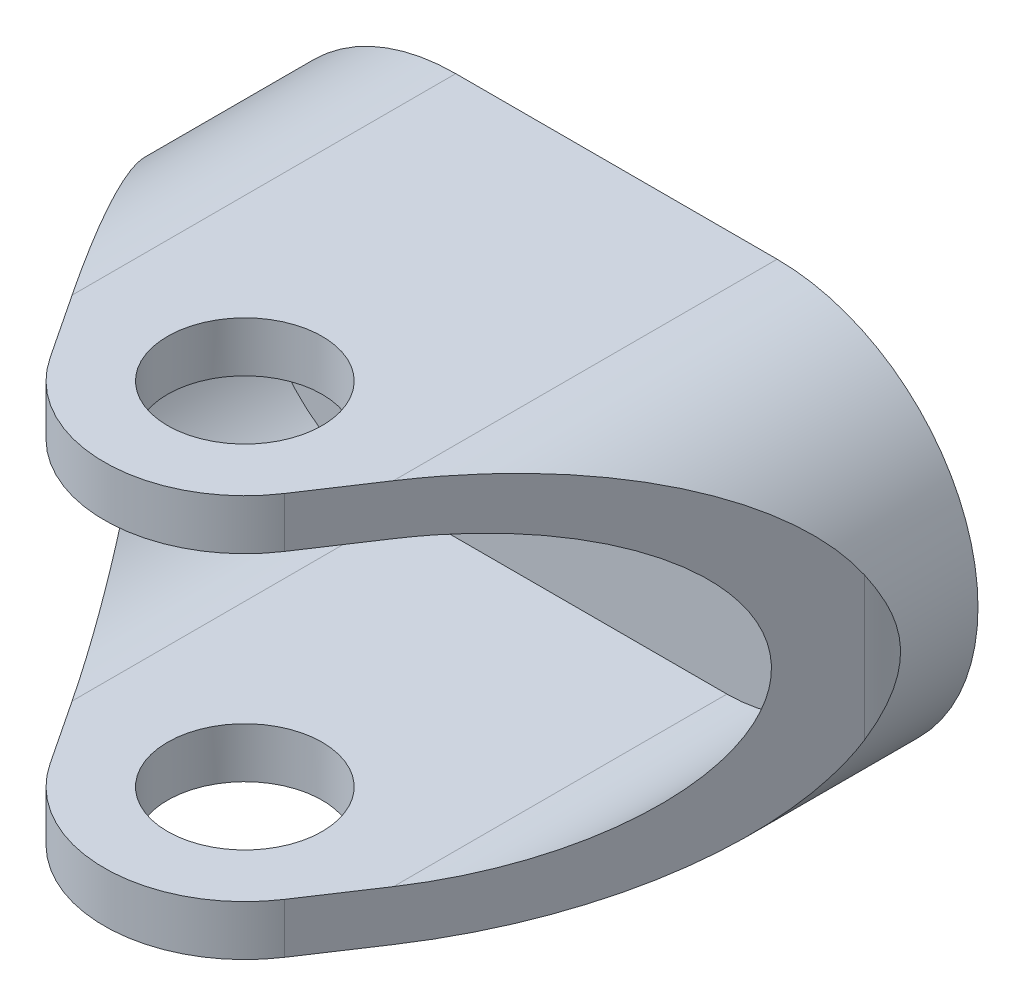
SolidWorks part; units mm, degrees
material "6061 Alloy"
ref_plane "Front Plane" through (0, 0, 0) normal (0, 0, 1) x (1, 0, 0)
ref_plane "Top Plane" through (0, 0, 0) normal (0, 1, 0) x (1, 0, 0)
ref_plane "Right Plane" through (0, 0, 0) normal (1, 0, 0) x (0, 0, -1)
sketch "Sketch1" plane through (0, 0, 0) normal (0, 1, 0) x (1, 0, 0)
  line L0 (-24.13, -19.05) -> (24.13, -19.05)
  line L1 (-24.13, -19.05) -> (-24.13, 19.05)
  line L2 (24.13, -19.05) -> (24.13, 19.05)
  line L3 (-24.13, 19.05) -> (24.13, 19.05)
  line L4 (-24.13, -19.05) -> (24.13, 19.05) construction
  line L5 (24.13, -19.05) -> (-24.13, 19.05) construction
  point P1 (0, 0)
  dimension "D1" = 38.1
  dimension "D2" = 48.26
extrude "Billet" add sketch "Sketch1" along normal blind 25.4
sketch "Sketch2" plane through (0, 25.4, 0) normal (0, 1, 0) x (1, 0, 0)
  line L1 (-7.4106, -9.3557) -> (-24.13, 15.875)
  line L3 (24.13, 19.05) -> (-24.13, 19.05) construction
  line L4 (-24.13, 15.875) -> (24.13, 15.875) construction
  line L5 (0, -14.605) -> (0, -11.9174) construction
  line L6 (-24.13, 15.875) -> (-24.13, -19.05)
  line L7 (-24.13, -19.05) -> (24.13, -19.05)
  line L8 (24.13, -19.05) -> (24.13, 15.875)
  line L9 (7.4106, -9.3557) -> (24.13, 15.875)
  arc A0 (7.4106, -9.3557) -> (-7.4106, -9.3557) centre (0, -4.445) cw
  circle A1 centre (0, -4.445) radius 4.8895
  line M1 (-24.13, 19.05) -> (-24.13, -19.05)
  line M2 (-24.13, -19.05) -> (24.13, -19.05)
  line M3 (24.13, -19.05) -> (24.13, 19.05)
  dimension "D1" = 8.89
  dimension "D3" = 9.779
  dimension "D2" = 3.175
  dimension "D4" = 20.32
extrude "Mill Cut 1" cut sketch "Sketch2" against normal through all contours L9 A0 L1 M1 M2 M3 | A1 region at (0, 25.4, 13.9307) region at (0, 25.4, 4.445)
fillet "Fillet2" radius 12.7 2 edges at (-24.13, 12.7, -15.875) (24.13, 12.7, -15.875)
fillet "Fillet1" [suppressed] radius 1.27
ref_plane "Plane2" through (0, 25.4, 13.335) normal (0, 0, 1) x (1, 0, 0)
sketch "Sketch6" plane through (0, 25.4, 13.335) normal (0, 0, 1) x (1, 0, 0)
  line L0 (7.4106, 0) -> (-7.4106, 0) construction
  line L1 (-10.16, -3.175) -> (10.16, -3.175)
  line L2 (-10.16, -3.175) -> (-10.16, -22.225)
  line L3 (-10.16, -22.225) -> (10.16, -22.225)
  line L4 (10.16, -3.175) -> (10.16, -22.225)
  line L5 (0, -3.175) -> (0, 0) construction
  line L6 (0, -22.225) -> (0, -25.4) construction
  line L7 (-24.13, 0) -> (-24.13, -25.4) construction
  arc A0 (-10.16, -3.175) -> (-10.16, -22.225) centre (-10.16, -12.7) ccw
  arc A1 (10.16, -3.175) -> (10.16, -22.225) centre (10.16, -12.7) cw
  point P6 (0, 0)
  point P7 (0, -3.175)
  dimension "D1" = 3.175
  dimension "D2" = 13.97
extrude "Cut-Extrude1" cut sketch "Sketch6" against normal offset from surface (29.21 mm away) 3.175 up to face at (0, 12.7, -19.05)
sketch "Sketch8" plane through (0, 25.4, 13.335) normal (0, 0, 1) x (1, 0, 0)
  line L7 (-7.4106, 0) -> (-22.0347, 0) construction
  line L8 (-10.16, -25.4) -> (-60.96, -25.4)
  line L9 (-60.96, -25.4) -> (-60.96, 0)
  line L10 (-60.96, 0) -> (-10.16, 0)
  line L11 (-7.4106, -25.4) -> (-22.0347, -25.4) construction
  arc A4 (-10.16, 0) -> (-10.16, -25.4) centre (-10.16, -12.7) ccw
  arc A8 (-10.16, -3.175) -> (-10.16, -22.225) centre (-10.16, -12.7) ccw construction
  point P3 (-11.43, -28.3505)
  point P7 (-11.43, -25.4)
  point P10 (0, 0)
  point P11 (-11.43, 0)
  point P12 (-14.5895, 0)
  dimension "D1" = 50.8
extrude "Cut-Extrude2" cut sketch "Sketch8" against normal through all
mirror "Mirror1" about plane through (0, 0, 0) normal (1, 0, 0) of "Cut-Extrude2"
sketch "Sketch9" plane through (0, 0, -15.875) normal (0, 0, 1) x (1, 0, 0)
  line L0 (0, 25.4) -> (0, 0) construction
  line L1 (7.4106, 25.4) -> (-7.4106, 25.4) construction
  line L2 (0, 12.7) -> (12.7, 12.7) construction
  circle A0 centre (12.7, 12.7) radius 3.175
  circle A1 centre (-12.7, 12.7) radius 3.175
  dimension "D1" = 6.35
  dimension "D2" = 12.7
extrude "Holes" cut sketch "Sketch9" against normal through all
ref_axis "Axis1" [suppressed] through (0, 22.225, 4.445) along (0, 1, 0)
ref_plane "Plane1" [suppressed] through (1.4286, 0, 0.52) normal (-0.9397, 0, -0.342) x (0, 1, 0)
sketch "Sketch5" [suppressed] plane through (0, 25.4, 0) normal (0, 1, 0) x (1, 0, 0)
  circle A0 centre (0, -4.445) radius 4.8895
extrude "Mock Bolt" [suppressed] add sketch "Sketch5" against normal through all
